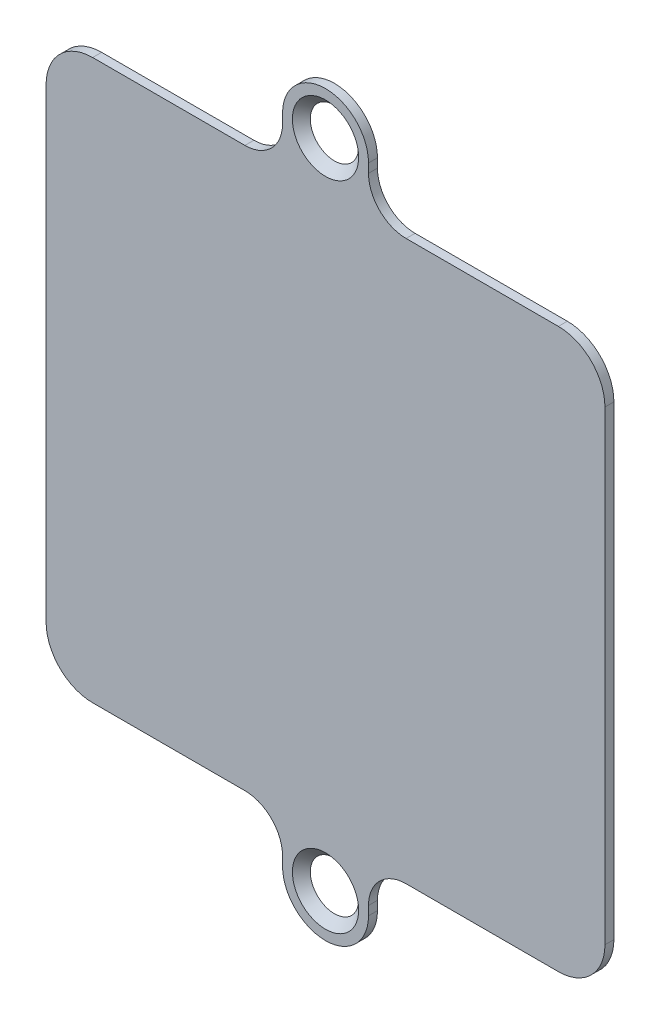
SolidWorks part; units mm, degrees
material "Нержавеющая сталь (ферритная)"
ref_plane "Спереди" through (0, 0, 0) normal (0, 0, 1) x (1, 0, 0)
ref_plane "Сверху" through (0, 0, 0) normal (0, 1, 0) x (1, 0, 0)
ref_plane "Справа" through (0, 0, 0) normal (1, 0, 0) x (0, 0, -1)
sketch "Эскиз1" plane through (0, 0, 0) normal (0, 0, 1) x (1, 0, 0)
  line L0 (-4.5, 15.7) -> (-12.5, 15.7) construction
  line L2 (2.5, -17.7) -> (2.5, -18.2) construction
  line L3 (-2.5, -18.2) -> (-2.5, -17.7) construction
  line L4 (4.5, -15.7) -> (12.5, -15.7) construction
  line L5 (-15.6, 13) -> (-15.6, -13)
  line L6 (-13, -15.6) -> (-12.5, -15.6)
  line L7 (-12.5, -15.6) -> (-4.5, -15.6)
  line L8 (0, -15.7) -> (0, 15.2) construction
  line L9 (-2.4, -18.2) -> (-2.4, -17.7)
  line L10 (2.5, 17.7) -> (2.5, 18.2) construction
  line L11 (2.5, 18.2) -> (-2.5, 18.2) construction
  line L12 (-2.5, 18.2) -> (-2.5, 17.7) construction
  line L13 (2.4, -17.7) -> (2.4, -18.2)
  line L14 (4.5, -15.6) -> (12.5, -15.6)
  line L15 (12.5, -15.6) -> (13, -15.6)
  line L16 (15.6, -13) -> (15.6, 13)
  line L17 (13, 15.6) -> (12.5, 15.6)
  line L18 (12.5, 15.6) -> (4.5, 15.6)
  line L19 (2.4, 17.7) -> (2.4, 18.2)
  line L20 (-2.4, 18.2) -> (-2.4, 17.7)
  line L21 (-4.5, 15.6) -> (-12.5, 15.6)
  line L22 (-12.5, 15.6) -> (-13, 15.6)
  line L24 (-15.7, 13) -> (-15.7, -13) construction
  line L25 (-13, -15.7) -> (-12.5, -15.7) construction
  line L26 (-12.5, -15.7) -> (-4.5, -15.7) construction
  line L27 (12.5, -15.7) -> (13, -15.7) construction
  line L28 (15.7, -13) -> (15.7, 13) construction
  line L29 (13, 15.7) -> (12.5, 15.7) construction
  line L30 (12.5, 15.7) -> (4.5, 15.7) construction
  line L31 (-12.5, 15.7) -> (-13, 15.7) construction
  arc A0 (2.5, 18.2) -> (-2.5, 18.2) centre (0, 18.2) ccw construction
  circle A1 centre (0, 18.2) radius 1
  arc A2 (-4.5, 15.7) -> (-2.5, 17.7) centre (-4.5, 17.7) ccw construction
  arc A3 (4.5, 15.7) -> (2.5, 17.7) centre (4.5, 17.7) cw construction
  circle A4 centre (0, -18.2) radius 1
  arc A5 (4.5, -15.7) -> (2.5, -17.7) centre (4.5, -17.7) ccw construction
  arc A6 (2.5, -18.2) -> (-2.5, -18.2) centre (0, -18.2) cw construction
  arc A7 (-4.5, -15.7) -> (-2.5, -17.7) centre (-4.5, -17.7) cw construction
  arc A8 (-15.6, -13) -> (-13, -15.6) centre (-13, -13) ccw
  arc A9 (-4.5, -15.6) -> (-2.4, -17.7) centre (-4.5, -17.7) cw
  arc A10 (2.4, -18.2) -> (-2.4, -18.2) centre (0, -18.2) cw
  arc A11 (4.5, -15.6) -> (2.4, -17.7) centre (4.5, -17.7) ccw
  arc A12 (-13, 15.7) -> (-15.7, 13) centre (-13, 13) ccw construction
  arc A13 (-15.7, -13) -> (-13, -15.7) centre (-13, -13) ccw construction
  arc A14 (13, -15.7) -> (15.7, -13) centre (13, -13) ccw construction
  arc A15 (15.7, 13) -> (13, 15.7) centre (13, 13) ccw construction
  arc A16 (13, -15.6) -> (15.6, -13) centre (13, -13) ccw
  arc A17 (15.6, 13) -> (13, 15.6) centre (13, 13) ccw
  arc A18 (4.5, 15.6) -> (2.4, 17.7) centre (4.5, 17.7) cw
  arc A19 (2.4, 18.2) -> (-2.4, 18.2) centre (0, 18.2) ccw
  arc A20 (-4.5, 15.6) -> (-2.4, 17.7) centre (-4.5, 17.7) ccw
  arc A21 (-13, 15.6) -> (-15.6, 13) centre (-13, 13) ccw
  point P11 (-2.5, 15.7)
  dimension "D4" = 2
  dimension "D5" = 2
  dimension "D6" = 2
  dimension "D2" = 2.5
  dimension "D3" = 2.5
  dimension "D1" = 0.1
extrude "Бобышка-Вытянуть1" add sketch "Эскиз1" along normal blind 0.5
chamfer "Фаска1" distance 0.85 angle 45 2 edges at (-1, -18.2, 0.5) (1, 18.2, 0.5)
scale "Масштаб1" scale about centroid uniform scaling yes scale factor 1.08
